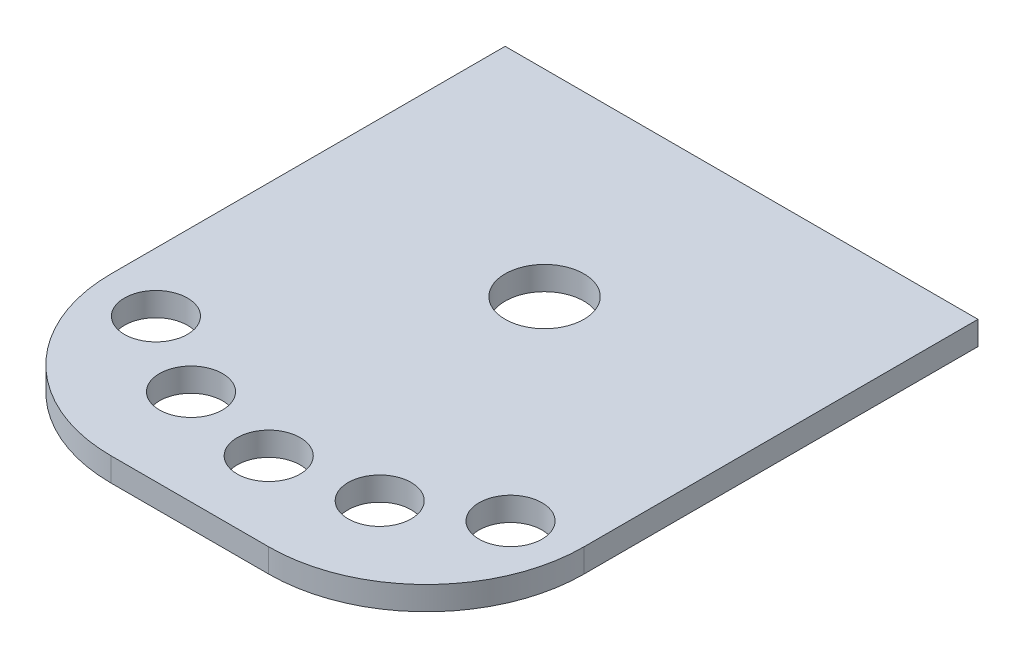
SolidWorks part; units mm, degrees
ref_plane "Plano frontal" through (0, 0, 0) normal (0, 0, 1) x (1, 0, 0)
ref_plane "Plano superior" through (0, 0, 0) normal (0, 1, 0) x (1, 0, 0)
ref_plane "Plano direito" through (0, 0, 0) normal (1, 0, 0) x (0, 0, -1)
sketch "Esboço1" plane through (0, 0, 0) normal (0, 1, 0) x (1, 0, 0)
  line L0 (30, 25) -> (30, -10) construction
  line L1 (0, 0) -> (60, 0) construction
  line L2 (0, 0) -> (0, 50)
  line L3 (0, 50) -> (60, 50)
  line L4 (60, 0) -> (60, 50)
  line L7 (0, 0) -> (60, 50) construction
  line L9 (0, 0) -> (60, 0) construction
  line L11 (20, -20) -> (40, -20)
  circle A4 centre (30, -10) radius 4
  arc A9 (40, -20) -> (60, 0) centre (40, 0) ccw
  arc A10 (0, 0) -> (20, -20) centre (20, 0) ccw
  circle A15 centre (18.0293, -7.8892) radius 4
  circle A16 centre (7.5024, -1.8116) radius 4
  circle A17 centre (52.4976, -1.8116) radius 4
  circle A18 centre (41.9707, -7.8892) radius 4
  circle A19 centre (30, 25) radius 5
  dimension "D1" = 10
  dimension "D2" = 8
  dimension "D8" = 20
  dimension "D4" = 60
  dimension "D5" = 50
  dimension "D7" = 35
  dimension "D9" = 20
  dimension "D6" = 3
base flange "Flange-base1" sketch "Esboço1" thickness 3 reverse thickness direction no parameters "D1"=0.7366
sketch "Curva-Linhas1" [suppressed] plane through (0, 0, 0) normal (0, 1, 0) x (1, 0, 0)
sketch "Caixa delimitadora1" [suppressed] plane through (0, 0, 0) normal (0, 1, 0) x (1, 0, 0)
sheet metal parameters "Chapa metálica1" thickness 3 parameters "D1"=0.7366
flat pattern "Padrão-Plano1" [suppressed]
sketch "Curva-Linhas2" plane through (0, 0, 0) normal (0, 1, 0) x (1, 0, 0)
sketch3d "Caixa delimitadora2" [suppressed]
  line L0 (-20, 50, 0) -> (-20, -20, 0) construction
  line L1 (40, 50, 0) -> (40, -20, 0) construction
  line L2 (-20, 50, 0) -> (40, 50, 0) construction
  line L3 (-20, -20, 0) -> (40, -20, 0) construction
